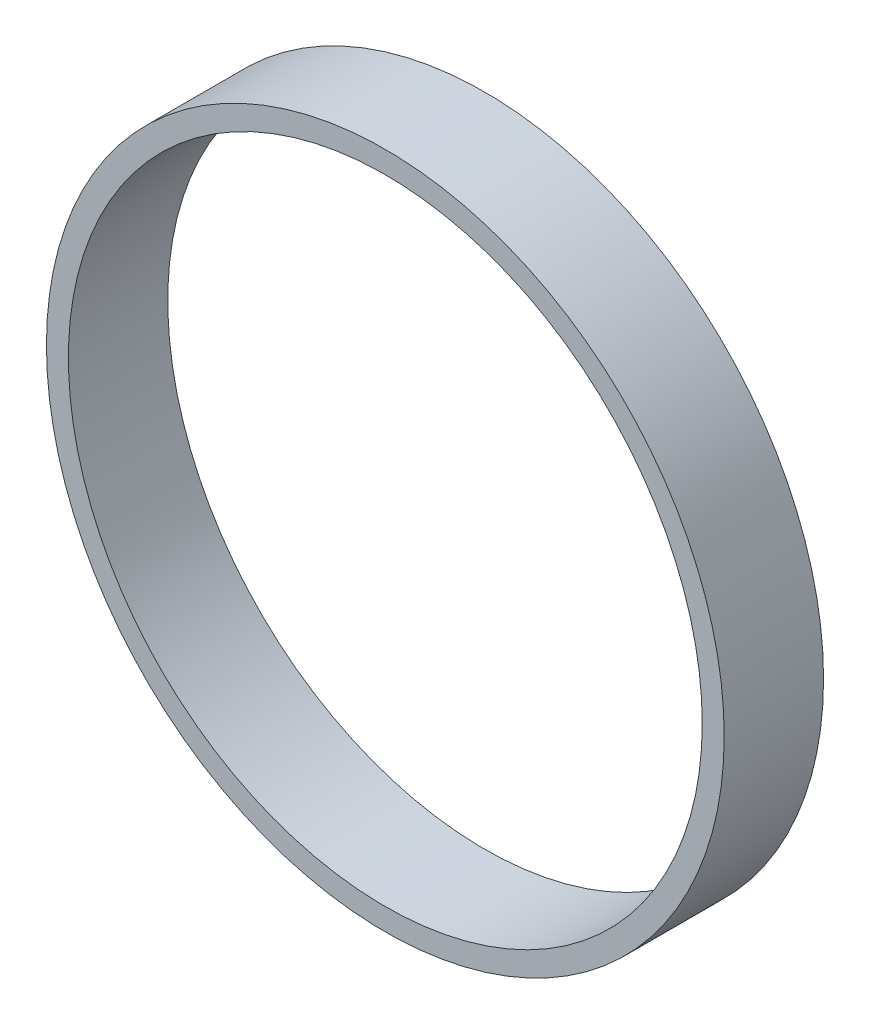
SolidWorks part; units mm, degrees
ref_plane "Front Plane" through (0, 0, 0) normal (0, 0, 1) x (1, 0, 0)
ref_plane "Top Plane" through (0, 0, 0) normal (0, 1, 0) x (1, 0, 0)
ref_plane "Right Plane" through (0, 0, 0) normal (1, 0, 0) x (0, 0, -1)
sketch "Sketch1" plane through (0, 0, 0) normal (0, 0, 1) x (1, 0, 0)
  circle A0 centre (0, 0) radius 31.9
  circle A1 centre (0, 0) radius 34.11
  dimension "D1" = 63.8
  dimension "D2" = 68.22
extrude "Boss-Extrude1" add sketch "Sketch1" along normal blind 10
